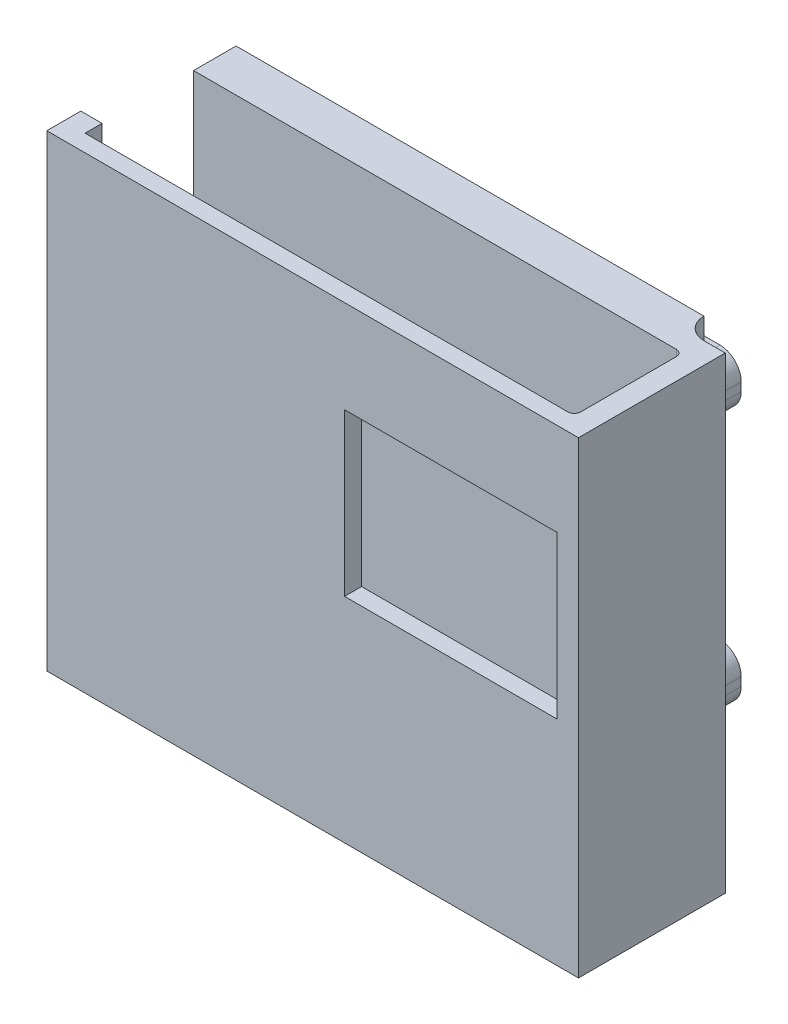
SolidWorks part; units mm, degrees
ref_plane "Front Plane" through (0, 0, 0) normal (1, 0, 0) x (0, 1, 0)
ref_plane "Top Plane" through (0, 0, 0) normal (0, 0, 1) x (0, 1, 0)
ref_plane "Right Plane" through (0, 0, 0) normal (0, 1, 0) x (-1, 0, 0)
sketch "Sketch2" plane through (0, 0, 0) normal (0, 0, 1) x (0, 1, 0)
  line L0 (-7.2, 11.5) -> (-7.2, -11.5)
  line L1 (-7.2, 11.5) -> (7.2, 11.5) construction
  line L2 (-7.2, 11.5) -> (-7.2, -11.5) construction
  line L3 (-7.2, -11.5) -> (7.2, -11.5) construction
  line L4 (7.2, 11.5) -> (7.2, -11.5) construction
  line L5 (-7.2, 11.5) -> (7.2, -11.5) construction
  line L6 (-7.2, -11.5) -> (7.2, 11.5) construction
  line L7 (-7.2, -11.5) -> (-4.8, -11.5)
  line L8 (-7.2, 11.5) -> (-4.8, 11.5)
  line L9 (-4.8, 11.5) -> (-4.8, 6.5)
  line L10 (0, 11.5) -> (0, -11.5) construction
  line L11 (7.2, 11.5) -> (7.2, -11.5) construction
  line L12 (4.8, 11.5) -> (4.8, 6.5)
  line L13 (7.2, 11.5) -> (4.8, 11.5)
  line L14 (7.2, -11.5) -> (4.8, -11.5)
  line L15 (7.2, 11.5) -> (7.2, -11.5)
  line L16 (-4.8, 6.5) -> (4.8, 6.5)
  line L17 (-4.8, -11.5) -> (-4.8, -10)
  line L18 (4.8, -11.5) -> (4.8, -10)
  line L19 (4.8, -10) -> (-4.8, -10)
  point P0 (0, 0)
  dimension "D1" = 14.4
  dimension "D2" = 23
  dimension "D3" = 2.4
  dimension "D4" = 5
  dimension "D5" = 1.5
extrude "Boss-Extrude1" add sketch "Sketch2" along normal blind 1
fillet "Fillet2" radius 1 8 edges at (11.5, -7.2, 0.5) (11.5, -4.8, 0.5) (11.5, 4.8, 0.5) (11.5, 7.2, 0.5) (-11.5, 7.2, 0.5) (-11.5, 4.8, 0.5) (-11.5, -7.2, 0.5) (-11.5, -4.8, 0.5)
sketch "Sketch3" plane through (0, 0, 1) normal (0, 0, 1) x (1, 0, 0)
  line L0 (-6.5, 0) -> (10, 0) construction
  line L1 (-6.5, 4.8) -> (-6.5, -4.8) construction
  line L2 (10, -4.8) -> (10, 4.8) construction
  line L4 (-3.25, 3.5) -> (6.75, 3.5)
  line L5 (-3.25, 3.5) -> (-3.25, -3.5)
  line L6 (-3.25, -3.5) -> (6.75, -3.5)
  line L7 (6.75, 3.5) -> (6.75, -3.5)
  line L8 (-3.25, 3.5) -> (6.75, -3.5) construction
  line L9 (-3.25, -3.5) -> (6.75, 3.5) construction
  point P6 (1.75, 0)
  dimension "D1" = 7
  dimension "D2" = 10
extrude "Boss-Extrude2" add sketch "Sketch3" along normal blind 2
sketch "Sketch4" plane through (0, 0, 3) normal (0, 0, 1) x (1, 0, 0)
  line L0 (1.75, 3.5) -> (1.75, -3.5) construction
  line L1 (6.75, 3.5) -> (-3.25, 3.5) construction
  line L2 (-3.25, -3.5) -> (6.75, -3.5) construction
  line L4 (-9.25, 11) -> (12.75, 11)
  line L5 (-9.25, 11) -> (-9.25, -11)
  line L6 (-9.25, -11) -> (12.75, -11)
  line L7 (12.75, 11) -> (12.75, -11)
  line L8 (-9.25, 11) -> (12.75, -11) construction
  line L9 (-9.25, -11) -> (12.75, 11) construction
  point P6 (1.75, 0)
  dimension "D1" = 22
extrude "Boss-Extrude3" add sketch "Sketch4" along normal blind 2
sketch "Sketch5" plane through (12.75, 0, 0) normal (1, 0, 0) x (0, 1, 0)
  line L0 (11, 5) -> (11, 3) construction
  line L1 (-11, 5) -> (11, 5)
  line L2 (-11, 5) -> (-11, 4)
  line L3 (-11, 4) -> (11, 4)
  line L4 (11, 5) -> (11, 4)
extrude "Boss-Extrude4" add sketch "Sketch5" along normal blind 2
sketch "Sketch6" plane through (0, 0, 5) normal (0, 0, 1) x (1, 0, 0)
  line L0 (-9.25, -11) -> (14.75, -11) construction
  line L1 (14.75, 11) -> (13.75, 11)
  line L2 (14.75, 11) -> (14.75, -11)
  line L3 (14.75, -11) -> (13.75, -11)
  line L4 (13.75, 11) -> (13.75, -11)
  dimension "D1" = 1
extrude "Boss-Extrude5" add sketch "Sketch6" along normal blind 5.1
fillet "Fillet4" radius 1 1 edges at (12.75, 0, 4)
fillet "Fillet5" radius 0.3 1 edges at (13.75, 0, 5)
sketch "Sketch7" plane through (0, 0, 10.1) normal (0, 0, 1) x (1, 0, 0)
  line L1 (14.75, 11) -> (-10.25, 11)
  line L2 (14.75, 11) -> (14.75, -11)
  line L3 (14.75, -11) -> (-10.25, -11)
  line L4 (-10.25, 11) -> (-10.25, -11)
  dimension "D1" = 25
extrude "Boss-Extrude6" add sketch "Sketch7" along normal blind 0.8
fillet "Fillet6" radius 0.3 1 edges at (13.75, 0, 10.1)
sketch "Sketch8" plane through (0, 0, 10.9) normal (0, 0, 1) x (1, 0, 0)
  line L0 (14.75, -11) -> (14.75, 6.64) construction
  line L1 (14.75, -11) -> (14.75, 11) construction
  line L2 (14.75, 6.64) -> (13.75, 6.64) construction
  line L8 (13.75, 6.64) -> (3.75, 6.64)
  line L9 (13.75, 6.64) -> (13.75, -0.96)
  line L10 (13.75, -0.96) -> (3.75, -0.96)
  line L11 (3.75, 6.64) -> (3.75, -0.96)
  dimension "D1" = 17.64
  dimension "D2" = 1
  dimension "D3" = 10
  dimension "D4" = 7.6
extrude "Cut-Extrude1" cut sketch "Sketch8" against normal blind 2
sketch "Sketch9" plane through (0, 0, 10.1) normal (0, 0, -1) x (1, 0, 0)
  line L1 (-10.25, 11) -> (-9.25, 11)
  line L2 (-10.25, 11) -> (-10.25, -11)
  line L3 (-10.25, -11) -> (-9.25, -11)
  line L4 (-9.25, 11) -> (-9.25, -11)
extrude "Boss-Extrude7" add sketch "Sketch9" along normal blind 0.8
